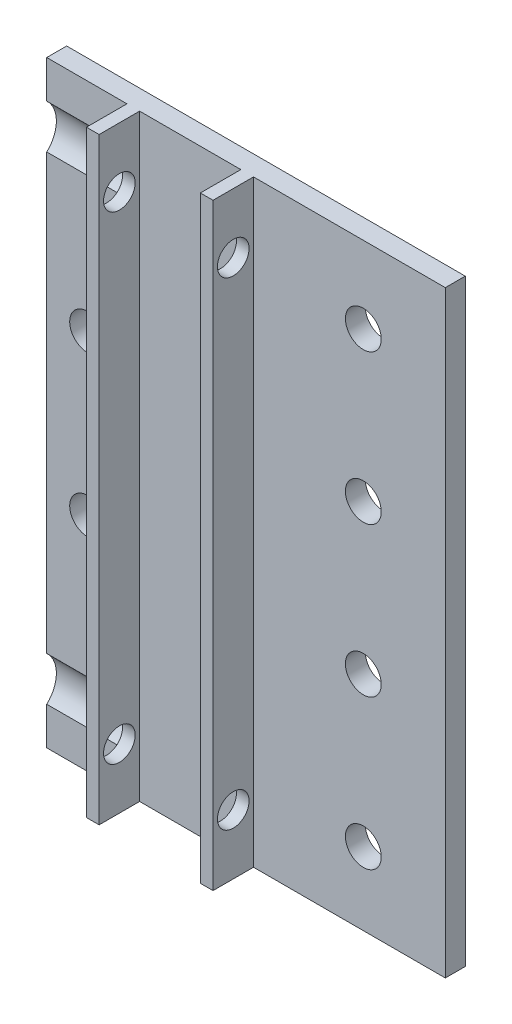
SolidWorks part; units mm, degrees
ref_plane "Front Plane" through (0, 0, 0) normal (0, 0, 1) x (1, 0, 0)
ref_plane "Top Plane" through (0, 0, 0) normal (0, 1, 0) x (1, 0, 0)
ref_plane "Right Plane" through (0, 0, 0) normal (1, 0, 0) x (0, 0, -1)
sketch "Sketch2" plane through (0, 0, 0) normal (0, 0, 1) x (1, 0, 0)
  line L0 (-123.0109, -74.4947) -> (-143.5848, -74.4947) construction
  line L1 (-123.0109, 0.5053) -> (-223.0109, 0.5053)
  line L2 (-123.0109, 0.5053) -> (-123.0109, -149.4947)
  line L3 (-123.0109, -149.4947) -> (-223.0109, -149.4947)
  line L4 (-223.0109, 0.5053) -> (-223.0109, -149.4947)
  line L5 (-143.5848, -74.4947) -> (-143.5848, -56.25) construction
  line L7 (-212.756, -54.0129) -> (-223.0109, -54.0129) construction
  line L8 (-212.756, -94.0129) -> (-223.0109, -94.0129) construction
  line L10 (-143.5848, -56.25) -> (-143.5848, -18.75) construction
  line L11 (-143.5848, -74.4947) -> (-143.5848, -93.75) construction
  line L12 (-143.5848, -93.75) -> (-143.5848, -131.25) construction
  circle A3 centre (-212.756, -54.0129) radius 4.165
  circle A4 centre (-212.756, -94.0129) radius 4.165
  circle A5 centre (-143.5848, -18.75) radius 3.15
  circle A6 centre (-143.5848, -56.25) radius 3.15
  circle A7 centre (-143.5848, -93.75) radius 3.15
  circle A8 centre (-143.5848, -131.25) radius 3.15
  dimension "D1" = 100
  dimension "D2" = 150
extrude "Boss-Extrude1" add sketch "Sketch2" along normal blind 5 contours L4 L3 L2 L1
sketch "Sketch3" plane through (0, 0, 0) normal (0, 0, -1) x (-1, 0, 0)
  circle A3 centre (212.756, -54.0129) radius 4.5
  circle A4 centre (212.756, -94.0129) radius 4.5
  circle A5 centre (143.5848, -18.75) radius 4.5
  circle A6 centre (143.5848, -56.25) radius 4.5
  circle A7 centre (143.5848, -93.75) radius 4.5
  circle A8 centre (143.5848, -131.25) radius 4.5
  dimension "D1" = 9
extrude "Cut-Extrude1" cut sketch "Sketch3" against normal blind 5
sketch "Sketch5" plane through (0, -149.4947, 0) normal (0, -1, 0) x (1, 0, 0)
  line L0 (-123.0109, 5) -> (-223.0109, 5) construction
  line L1 (-202.8859, 5) -> (-199.7109, 5)
  line L2 (-202.8859, 5) -> (-202.8859, 15.16)
  line L3 (-202.8859, 15.16) -> (-199.7109, 15.16)
  line L4 (-199.7109, 5) -> (-199.7109, 15.16)
  line L6 (-174.3109, 5) -> (-171.1359, 5)
  line L7 (-174.3109, 5) -> (-174.3109, 15.16)
  line L8 (-174.3109, 15.16) -> (-171.1359, 15.16)
  line L9 (-171.1359, 5) -> (-171.1359, 15.16)
  line L10 (-223.0109, 5) -> (-223.0109, 0) construction
  dimension "D1" = 23.3
  dimension "D2" = 25.4
  dimension "D3" = 3.175
  dimension "D4" = 10.16
extrude "Boss-Extrude2" add sketch "Sketch5" against normal up to surface (150 mm away) up to face at (-173.0109, 0.5053, 2.5)
sketch "Sketch7" plane through (-202.8859, 0, 0) normal (-1, 0, 0) x (0, 0, 1)
  line L0 (15.16, -149.4947) -> (5, -149.4947) construction
  line L1 (15.16, 0.5053) -> (15.16, -149.4947) construction
  line L2 (15.16, -74.4947) -> (0, -74.4947)
  line L3 (0, 0.5053) -> (0, -149.4947) construction
  circle A0 centre (10.08, -134.4947) radius 3.9687
  circle A1 centre (10.08, -14.4947) radius 3.9687
  dimension "D2" = 7.9375
  dimension "D1" = 15
  dimension "D3" = 5.08
extrude "Cut-Extrude2" cut sketch "Sketch7" against normal up to surface (31.75 mm away) contours A1 | A0 region at (-202.8859, -134.4947, 10.08) region at (-202.8859, -14.4947, 10.08) up to face at (-171.1359, -74.4947, 10.08)
sketch "Sketch8" plane through (-223.0109, 0, 0) normal (-1, 0, 0) x (0, 0, 1)
  circle A0 centre (10.08, -14.4947) radius 7.5
  circle A1 centre (10.08, -134.4947) radius 7.5
  point P5 (10.08, -134.4947)
  dimension "D1" = 15
extrude "Cut-Extrude3" cut sketch "Sketch8" against normal up to surface (20.125 mm away) up to face at (-202.8859, -74.4947, 10.08)
